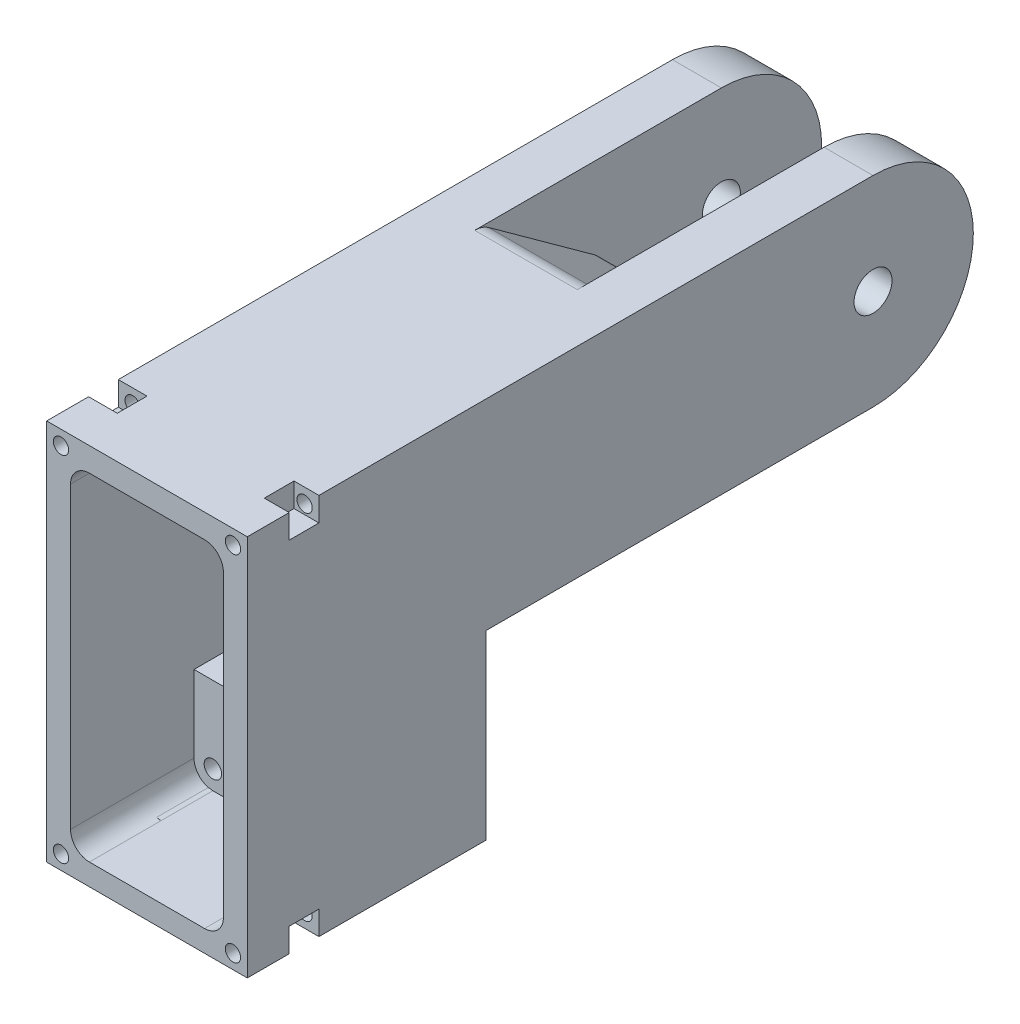
SolidWorks part; units mm, degrees
ref_plane "Front Plane" through (0, 0, 0) normal (0, 0, 1) x (1, 0, 0)
ref_plane "Top Plane" through (0, 0, 0) normal (0, 1, 0) x (1, 0, 0)
ref_plane "Right Plane" through (0, 0, 0) normal (1, 0, 0) x (0, 0, -1)
sketch "Sketch2" plane through (0, 0, 0) normal (0, 0, 1) x (1, 0, 0)
  line L1 (-21, 21) -> (21, 21)
  line L2 (-21, 21) -> (-21, -21)
  line L3 (-21, -21) -> (21, -21)
  line L4 (21, 21) -> (21, -21)
  line L5 (-21, 21) -> (21, -21) construction
  line L6 (-21, -21) -> (21, 21) construction
  point P0 (0, 0)
  dimension "D1" = 42
  dimension "D2" = 42
extrude "Boss-Extrude1" add sketch "Sketch2" along normal blind 60
ref_plane "Plane1" through (0, 0, 0) normal (0, 0, -1) x (-1, 0, 0)
sketch "Sketch3" plane through (0, 0, 0) normal (0, 0, -1) x (-1, 0, 0)
  line L0 (-21, 21) -> (21, 21) construction
  line L1 (21, -21) -> (10.75, -21)
  line L2 (21, -21) -> (21, 21)
  line L3 (21, 21) -> (10.75, 21)
  line L4 (10.75, -21) -> (10.75, 21)
  line L6 (-21, -21) -> (-10.75, -21)
  line L7 (-21, -21) -> (-21, 21)
  line L8 (-21, 21) -> (-10.75, 21)
  line L9 (-10.75, -21) -> (-10.75, 21)
  dimension "D1" = 10.25
  dimension "D2" = 10.25
extrude "Boss-Extrude2" add sketch "Sketch3" along normal blind 21
ref_plane "Plane2" through (-21, 0, 0) normal (-1, 0, 0) x (0, 0, 1)
sketch "Sketch4" plane through (-21, 0, 0) normal (-1, 0, 0) x (0, 0, 1)
  line L0 (-21, -21) -> (-21, 21)
  arc A0 (-21, -21) -> (-21, 21) centre (-21, 0) cw
  dimension "D1" = 21
extrude "Boss-Extrude3" add sketch "Sketch4" against normal blind 10.25
ref_plane "Plane3" through (21, 0, 0) normal (1, 0, 0) x (0, 0, -1)
sketch "Sketch5" plane through (21, 0, 0) normal (1, 0, 0) x (0, 0, -1)
  line L0 (21, 21) -> (21, -21)
  arc A0 (21, 21) -> (21, -21) centre (21, 0) cw
  dimension "D1" = 21
extrude "Boss-Extrude4" add sketch "Sketch5" against normal blind 10.25
ref_plane "Plane4" through (0, 0, 60) normal (0, 0, 1) x (1, 0, 0)
sketch "Sketch6" plane through (0, 0, 60) normal (0, 0, 1) x (1, 0, 0)
  line L0 (21, 21) -> (-21, 21) construction
  line L1 (-16, 16) -> (16, 16)
  line L2 (-16, 16) -> (-16, -16)
  line L3 (-16, -16) -> (16, -16)
  line L4 (16, 16) -> (16, -16)
  line L5 (-16, 16) -> (16, -16) construction
  line L6 (-16, -16) -> (16, 16) construction
  line L7 (21, -21) -> (21, 21) construction
  point P0 (0, 0)
  dimension "D1" = 5
  dimension "D2" = 5
extrude "Cut-Extrude1" cut sketch "Sketch6" against normal blind 27
ref_plane "Plane5" through (10.75, 0, 0) normal (-1, 0, 0) x (0, 0, 1)
sketch "Sketch7" plane through (10.75, 0, 0) normal (-1, 0, 0) x (0, 0, 1)
  line L0 (0, -21) -> (0, 21) construction
  circle A0 centre (-21, 0) radius 3.975
  dimension "D2" = 7.95
  dimension "D1" = 21
extrude "Cut-Extrude2" cut sketch "Sketch7" against normal through all
ref_plane "Plane6" through (-10.75, 0, 0) normal (1, 0, 0) x (0, 0, -1)
sketch "Sketch9" plane through (-10.75, 0, 0) normal (1, 0, 0) x (0, 0, -1)
  line L0 (0, 21) -> (0, -21) construction
  circle A0 centre (21, 0) radius 3.975
  dimension "D2" = 7.95
  dimension "D1" = 21
extrude "Cut-Extrude3" cut sketch "Sketch9" against normal through all
ref_plane "Plane9" through (10.75, 0, 0) normal (-1, 0, 0) x (0, 0, 1)
sketch "Sketch11" plane through (10.75, 0, 0) normal (-1, 0, 0) x (0, 0, 1)
  line L0 (0, 0) -> (0, 21)
  line L1 (0, 0) -> (0, -21)
  line L2 (0, -21) -> (29.0252, -21)
  line L3 (29.0252, -21) -> (0, 0)
  line L4 (0, -21) -> (0, 21) construction
  line L5 (0, 21) -> (29.0252, 21) construction
  line L6 (29.0252, 21) -> (0, 0) construction
  line L7 (0, 0) -> (0, 21)
  line L8 (0, 0) -> (29.0252, 21)
  line L9 (29.0252, 21) -> (0, 21)
  line M5 (0, -21) -> (0, 21)
extrude "Cut-Extrude5" cut sketch "Sketch11" along normal blind 21.5 contours L8 L9 M5 | L1 L2 L3 region at (10.75, 14, 9.6751)
fillet "Fillet1" radius 5 1 edges at (0, 0, 0)
fillet "Fillet2" radius 5 1 edges at (0, -21, 29.0252)
fillet "Fillet3" radius 5 1 edges at (0, 21, 29.0252)
ref_plane "Plane10" through (0, 0, 60) normal (0, 0, 1) x (1, 0, 0)
sketch "Sketch12" plane through (0, 0, 60) normal (0, 0, 1) x (1, 0, 0)
  line L1 (21, 21) -> (-21, 21)
  line L2 (21, 21) -> (21, -59)
  line L3 (21, -59) -> (-21, -59)
  line L4 (-21, 21) -> (-21, -59)
  dimension "D1" = 80
  dimension "D2" = 42
extrude "Boss-Extrude5" add sketch "Sketch12" along normal blind 50
ref_plane "Plane11" through (0, 0, 110) normal (0, 0, 1) x (1, 0, 0)
sketch "Sketch13" plane through (0, 0, 110) normal (0, 0, 1) x (1, 0, 0)
  line L0 (21, 21) -> (-21, 21) construction
  line L1 (16, 16) -> (-16, 16)
  line L2 (16, 16) -> (16, -54.5)
  line L3 (16, -54.5) -> (-16, -54.5)
  line L4 (-16, 16) -> (-16, -54.5)
  line L6 (21, -59) -> (21, 21) construction
  dimension "D1" = 5
  dimension "D2" = 70.5
  dimension "D3" = 5
extrude "Cut-Extrude7" cut sketch "Sketch13" against normal blind 40.5 contours L4 L3 L2 L1
ref_plane "Plane12" through (0, -59, 0) normal (0, -1, 0) x (-1, 0, 0)
sketch "Sketch14" plane through (0, -59, 0) normal (0, -1, 0) x (-1, 0, 0)
  line L1 (13, -95) -> (-13, -95)
  line L2 (13, -95) -> (13, -84.1524)
  line L3 (13, -84.1524) -> (-13, -84.1524)
  line L4 (-13, -95) -> (-13, -84.1524)
  line L5 (13, -95) -> (-13, -84.1524) construction
  line L6 (13, -84.1524) -> (-13, -95) construction
  line L7 (21, -110) -> (-21, -110) construction
  line L8 (-21, -110) -> (-21, -60) construction
  line L9 (21, -110) -> (21, -60) construction
  point P0 (0, -89.5762)
  point P7 (-13, -89.5762)
  dimension "D1" = 15
  dimension "D2" = 8
  dimension "D3" = 8
extrude "Cut-Extrude8" cut sketch "Sketch14" against normal blind 40.5
ref_plane "Plane13" through (0, 0, 60) normal (0, 0, -1) x (-1, 0, 0)
sketch "Sketch15" plane through (0, 0, 60) normal (0, 0, -1) x (-1, 0, 0)
  line L0 (-21, -59) -> (-21, -21) construction
  line L1 (13, -44) -> (-13, -44)
  line L2 (13, -44) -> (13, -33.42)
  line L3 (13, -33.42) -> (-13, -33.42)
  line L4 (-13, -44) -> (-13, -33.42)
  line L5 (13, -44) -> (-13, -33.42) construction
  line L6 (13, -33.42) -> (-13, -44) construction
  line L7 (21, -21) -> (21, -59) construction
  line L8 (21, -59) -> (-21, -59) construction
  point P0 (0, -38.71)
  dimension "D1" = 8
  dimension "D2" = 8
  dimension "D3" = 10.58
  dimension "D4" = 15
extrude "Cut-Extrude9" cut sketch "Sketch15" against normal blind 40.5
ref_plane "Plane14" through (0, 0, 69.5) normal (0, 0, 1) x (1, 0, 0)
sketch "Sketch16" plane through (0, 0, 69.5) normal (0, 0, 1) x (1, 0, 0)
  circle A0 centre (11.995, 11.995) radius 1.825
  circle A1 centre (-11.995, 11.995) radius 1.825
  circle A2 centre (-11.995, -50.495) radius 1.825
  circle A3 centre (11.995, -50.495) radius 1.825
  dimension "D1" = 3.65
  dimension "D2" = 3.65
  dimension "D9" = 3.65
  dimension "D10" = 3.65
fillet "Fillet4" radius 3.95 4 edges at (-16, -54.5, 89.75) (16, -54.5, 89.75) (-16, 16, 89.75) (16, 16, 89.75)
extrude "Cut-Extrude10" cut sketch "Sketch16" against normal blind 20
ref_plane "Plane15" through (0, 0, 79.5) normal (0, 0, 1) x (1, 0, 0)
sketch "Sketch18" plane through (0, 0, 69.5) normal (0, 0, 1) x (1, 0, 0)
  line L0 (-13, -34.48) -> (-13, -44)
  line L1 (-13, -33.42) -> (-13, -44) construction
  line L2 (-13, -44) -> (13, -44)
  line L3 (13, -44) -> (13, -34.48)
  line L4 (13, -44) -> (13, -33.42) construction
  line L12 (-13, -34.48) -> (-16, -34.48)
  line L13 (-16, 12.05) -> (-16, -50.55) construction
  line L16 (-16, -34.48) -> (-16, -50.55)
  line L17 (13, -34.48) -> (16, -34.48)
  line L18 (16, 12.05) -> (16, -50.55) construction
  line L19 (16, -34.48) -> (16, -50.55)
  line L20 (12.05, -54.5) -> (-12.05, -54.5)
  arc A0 (-16, -50.55) -> (-12.05, -54.5) centre (-12.05, -50.55) ccw
  arc A1 (16, -50.55) -> (12.05, -54.5) centre (12.05, -50.55) cw
  circle A3 centre (12.05, -50.55) radius 1.83
  circle A4 centre (-12.05, -50.55) radius 1.8275
  dimension "D3" = 3.655
  dimension "D4" = 3.66
  dimension "D1" = 9.52
  dimension "D2" = 9.52
extrude "Boss-Extrude7" add sketch "Sketch18" along normal up to vertex (14.6524 mm away) up to point (-12.05, -54.5, 84.1524)
ref_plane "Plane20" through (0, 0, 110) normal (0, 0, 1) x (1, 0, 0)
sketch "Sketch19" plane through (0, 0, 110) normal (0, 0, 1) x (1, 0, 0)
  line L0 (21, 21) -> (-21, 21) construction
  line L1 (21, -59) -> (21, 21) construction
  line L2 (-21, 21) -> (-21, -59) construction
  line L3 (-21, -59) -> (21, -59) construction
  circle A0 centre (18, 18) radius 1.6
  circle A1 centre (-18, 18) radius 1.6
  circle A2 centre (-18, -56) radius 1.6
  circle A3 centre (18, -56) radius 1.6
  dimension "D1" = 3
  dimension "D2" = 3
  dimension "D3" = 3
  dimension "D4" = 3
  dimension "D5" = 3.2
  dimension "D6" = 3.2
  dimension "D7" = 3.2
  dimension "D8" = 3.2
  dimension "D9" = 3
  dimension "D10" = 3
  dimension "D11" = 3
  dimension "D12" = 3
extrude "Cut-Extrude11" cut sketch "Sketch19" against normal blind 30
ref_plane "Plane21" through (0, -59, 0) normal (0, -1, 0) x (-1, 0, 0)
sketch "Sketch23" plane through (0, -59, 0) normal (0, -1, 0) x (-1, 0, 0)
  line L0 (-21, -110) -> (-21, -60) construction
  line L11 (21, -110) -> (-21, -110) construction
  line L13 (-21, -95) -> (-15, -95)
  line L14 (-21, -95) -> (-21, -101.2218)
  line L15 (-21, -101.2218) -> (-15, -101.2218)
  line L16 (-15, -95) -> (-15, -101.2218)
  dimension "D2" = 15
  dimension "D3" = 6
extrude "Cut-Extrude14" cut sketch "Sketch23" against normal blind 5
sketch "Sketch25" plane through (0, -59, 0) normal (0, -1, 0) x (-1, 0, 0)
  line L0 (21, -110) -> (21, -60) construction
  line L1 (21, -95) -> (15, -95)
  line L2 (21, -95) -> (21, -101.22)
  line L3 (21, -101.22) -> (15, -101.22)
  line L4 (15, -95) -> (15, -101.22)
  line L5 (21, -110) -> (-21, -110) construction
  dimension "D1" = 6
  dimension "D2" = 15
  dimension "D3" = 8.78
  dimension "D4" = 6.22
extrude "Cut-Extrude15" cut sketch "Sketch25" against normal blind 5
ref_plane "Plane22" through (0, 21, 0) normal (0, 1, 0) x (1, 0, 0)
sketch "Sketch26" plane through (0, 21, 0) normal (0, 1, 0) x (1, 0, 0)
  line L0 (-21, -110) -> (-21, 21) construction
  line L1 (-21, -101.22) -> (-15, -101.22)
  line L2 (-21, -101.22) -> (-21, -95)
  line L3 (-21, -95) -> (-15, -95)
  line L4 (-15, -101.22) -> (-15, -95)
  line L5 (21, -110) -> (21, 21) construction
  line L6 (15.7781, -101.22) -> (21, -101.22)
  line L7 (15.7781, -101.22) -> (15.7781, -95)
  line L8 (15.7781, -95) -> (21, -95)
  line L9 (21, -101.22) -> (21, -95)
  line L10 (21, -110) -> (-21, -110) construction
  dimension "D1" = 6
  dimension "D2" = 15
  dimension "D3" = 8.78
  dimension "D4" = 6.22
  dimension "D5" = 8.78
  dimension "D6" = 15
extrude "Cut-Extrude16" cut sketch "Sketch26" against normal blind 5
ref_plane "Plane23" through (0, 0, 69.5) normal (0, 0, 1) x (1, 0, 0)
sketch "Sketch27" plane through (0, 0, 69.5) normal (0, 0, 1) x (1, 0, 0)
  line L3 (12.05, 16) -> (-12.05, 16) construction
  circle A1 centre (0, 4.5) radius 1.975
  dimension "D1" = 11.5
  dimension "D2" = 3.95
extrude "Cut-Extrude17" cut sketch "Sketch27" against normal blind 4
sketch "Sketch28" plane through (0, 0, 69.5) normal (0, 0, 1) x (1, 0, 0)
  line L0 (-16, 12.05) -> (-16, -34.48) construction
  line L1 (-16, -15.5) -> (16, -15.5)
  line L2 (-16, -15.5) -> (-16, -27.4554)
  line L3 (-16, -27.4554) -> (16, -27.4554)
  line L4 (16, -15.5) -> (16, -27.4554)
  line L5 (16, 12.05) -> (16, -34.48) construction
  circle A0 centre (0, 4.5) radius 1.975 construction
  dimension "D1" = 20
extrude "Cut-Extrude18" cut sketch "Sketch28" against normal blind 4
ref_plane "Plane24" through (0, 0, 95) normal (0, 0, -1) x (-1, 0, 0)
sketch "Sketch29" plane through (0, 0, 95) normal (0, 0, -1) x (-1, 0, 0)
  line L1 (13, -59) -> (-13, -59)
  line L2 (13, -59) -> (13, -54.3841)
  line L4 (-13, -59) -> (-13, -54.3841)
  line L5 (-12.05, -54.5) -> (-13, -54.3841)
  line L6 (-12.05, -54.5) -> (12.05, -54.5)
  line L8 (13, -54.3841) -> (12.05, -54.5)
extrude "Boss-Extrude8" add sketch "Sketch29" along normal up to vertex (10.8476 mm away) up to point (-13, -59, 84.1524)
sketch "Sketch30" plane through (0, 0, 69.5) normal (0, 0, 1) x (1, 0, 0)
  line L1 (-13, -3.92) -> (13, -3.92)
  line L2 (-13, -3.92) -> (-13, -14.5)
  line L3 (-13, -14.5) -> (13, -14.5)
  line L4 (13, -3.92) -> (13, -14.5)
  line L9 (16, 12.05) -> (16, -15.5) construction
  line L12 (12.05, 16) -> (-12.05, 16) construction
  dimension "D1" = 26
  dimension "D2" = 10.58
  dimension "D3" = 3
  dimension "D4" = 30.5
extrude "Cut-Extrude19" cut sketch "Sketch30" against normal blind 20
ref_plane "Plane25" through (0, -21, 0) normal (0, -1, 0) x (-1, 0, 0)
sketch "Sketch31" plane through (0, -21, 0) normal (0, -1, 0) x (-1, 0, 0)
  line L0 (-21, -60) -> (-21, 21) construction
  line L1 (16, -53.309) -> (-16, -53.309)
  line L2 (16, -53.309) -> (16, -42.729)
  line L3 (16, -42.729) -> (-16, -42.729)
  line L4 (-16, -53.309) -> (-16, -42.729)
  line L5 (16, -53.309) -> (-16, -42.729) construction
  line L6 (16, -42.729) -> (-16, -53.309) construction
  line L7 (21, -60) -> (21, 21) construction
  point P0 (0, -48.019)
  dimension "D1" = 5
  dimension "D2" = 5
  dimension "D3" = 10.58
extrude "Cut-Extrude20" cut sketch "Sketch31" against normal blind 20
ref_plane "Plane26" through (0, -44, 0) normal (0, 1, 0) x (1, 0, 0)
sketch "Sketch32" plane through (0, -44, 0) normal (0, 1, 0) x (1, 0, 0)
  line L0 (-13, -84.1524) -> (-13, -69.5024)
  line L1 (-13, -84.1524) -> (-13, -60) construction
  line L2 (-13, -69.5024) -> (13, -69.5024)
  line L3 (13, -84.1524) -> (13, -60) construction
  line L4 (13, -69.5024) -> (13, -84.1524)
  line L5 (13, -84.1524) -> (-13, -84.1524)
  dimension "D1" = 14.65
extrude "Boss-Extrude9" add sketch "Sketch32" along normal up to vertex (9.52 mm away) up to point (-13, -34.48, 84.1524)
sketch "Sketch33" plane through (0, 0, 69.5) normal (0, 0, 1) x (1, 0, 0)
  line L0 (13, -34.48) -> (13, -33.42) construction
  line L1 (-13, -33.42) -> (13, -33.42)
  line L2 (-13, -33.42) -> (-13, -34.48)
  line L3 (-13, -34.48) -> (13, -34.48)
  line L4 (13, -33.42) -> (13, -34.48)
extrude "Boss-Extrude10" add sketch "Sketch33" against normal up to vertex (9.5 mm away) up to point (-13, -33.42, 60)
